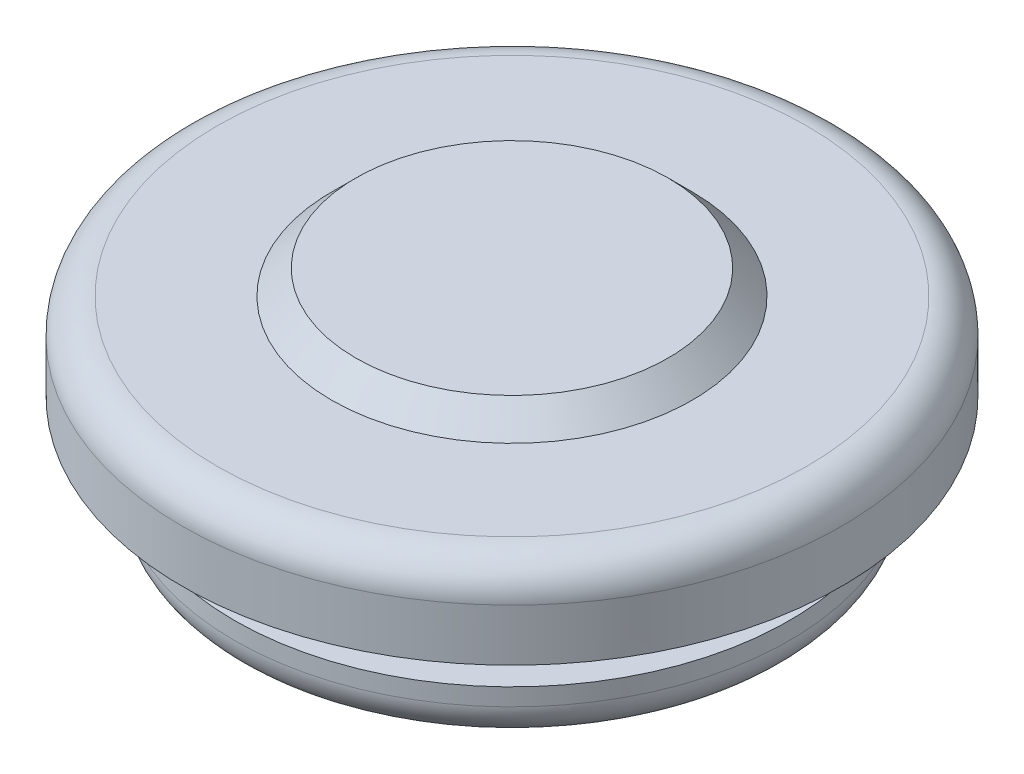
SolidWorks part; units mm, degrees
material "ｺﾞﾑ"
ref_plane "Front Plane" through (0, 0, 0) normal (0, 0, 1) x (1, 0, 0)
ref_plane "Top Plane" through (0, 0, 0) normal (0, 1, 0) x (1, 0, 0)
ref_plane "Right Plane" through (0, 0, 0) normal (1, 0, 0) x (0, 0, -1)
sketch "ｽｹｯﾁ1" plane through (0, 0, 0) normal (0, 0, 1) x (1, 0, 0)
  line L0 (0, 0) -> (0, 4.8052) construction
  line L2 (0, 6.3) -> (4.5, 6.3)
  line L3 (0, 6.3) -> (0, 5.6)
  line L4 (3.5, 0) -> (8, 0)
  line L5 (9.5, 5.6) -> (9.5, 3.1)
  line L6 (8, 1.5) -> (8, 0)
  line L7 (9.5, 3.1) -> (6, 3.1)
  line L10 (0, 5.6) -> (3.5, 5.6)
  line L11 (3.5, 0) -> (3.5, 5.6)
  line L13 (8, 1.5) -> (6, 1.5)
  line L15 (6, 3.1) -> (6, 1.5)
  line L17 (9.5, 5.6) -> (4.5, 5.6)
  line L18 (4.5, 6.3) -> (4.5, 5.6)
  point P1 (4.6655, 5.6)
  point P6 (3.5, 5.6)
  point P7 (2.6222, 1.6064)
  point P11 (1.75, 1.2609)
  point P16 (4.8812, 1.3982)
  point P26 (5.7637, 5.9793)
  dimension "D1" = 1.5
  dimension "D2" = 2.5
  dimension "D3" = 7
  dimension "D4" = 12
  dimension "D5" = 16
  dimension "D6" = 6.3
  dimension "D7" = 1.6
  dimension "D8" = 19
  dimension "D9" = 1
revolve "回転1" add sketch "ｽｹｯﾁ1" angle 360 about L0
fillet "ﾌｨﾚｯﾄ1" radius 1 2 edges at (0, 0, -8) (0, 5.6, -9.5)
chamfer "面取り1" distance 0.7 angle 45 1 edges at (0, 5.6, -4.5)
